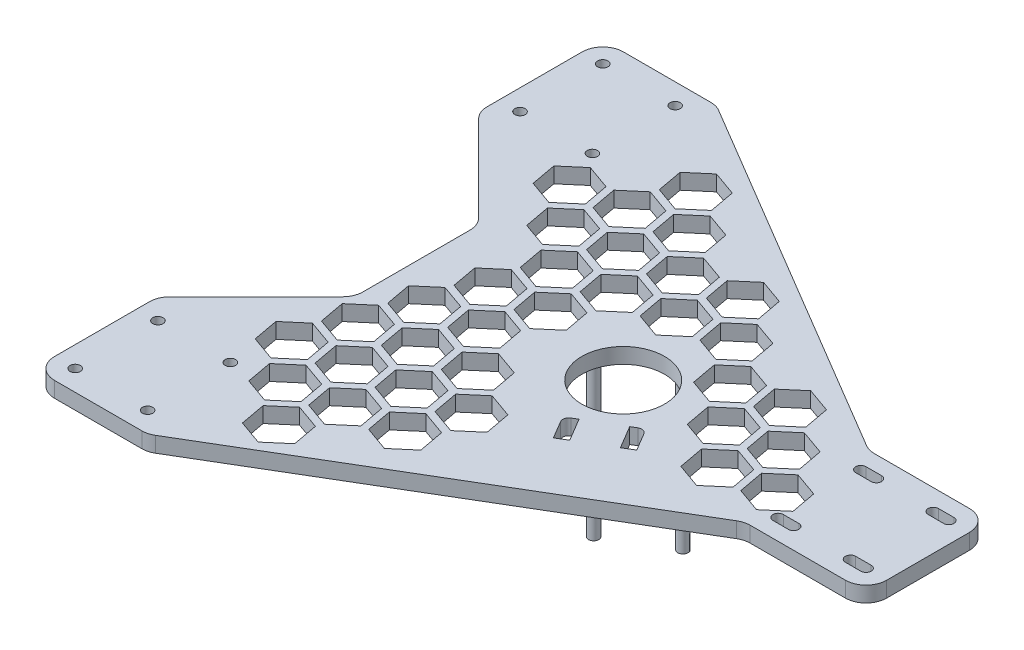
SolidWorks part; units mm, degrees
material "6061-O (SS)"
ref_plane "Plan de face" through (0, 0, 0) normal (0, 0, 1) x (1, 0, 0)
ref_plane "Plan de dessus" through (0, 0, 0) normal (0, 1, 0) x (1, 0, 0)
ref_plane "Plan de droite" through (0, 0, 0) normal (1, 0, 0) x (0, 0, -1)
sketch "Esquisse1" plane through (0, 0, 0) normal (0, 1, 0) x (1, 0, 0)
  line L1 (58.95, -55) -> (-58.95, -55)
  line L2 (58.95, -55) -> (58.95, 55)
  line L3 (58.95, 55) -> (-58.95, 55)
  line L4 (-58.95, -55) -> (-58.95, 55)
  line L5 (58.95, -55) -> (-58.95, 55) construction
  line L6 (58.95, 55) -> (-58.95, -55) construction
  point P0 (0, 0)
  dimension "D1" = 110
  dimension "D2" = 117.9
extrude "Boss.-Extru.1" add sketch "Esquisse1" along normal blind 3
sketch "Esquisse2" plane through (0, 0, 0) normal (0, 1, 0) x (1, 0, 0)
  line L0 (-58.95, -55) -> (58.95, -55) construction
  line L1 (-54.95, -35) -> (-40.95, -35) construction
  line L2 (-54.95, -35) -> (-54.95, -51) construction
  line L3 (-54.95, -51) -> (-40.95, -51) construction
  line L4 (-40.95, -35) -> (-40.95, -51) construction
  line L5 (-54.95, -35) -> (-40.95, -51) construction
  line L6 (-54.95, -51) -> (-40.95, -35) construction
  line L7 (-58.95, 55) -> (-58.95, -55) construction
  line L8 (0, 0) -> (-58.95, 0) construction
  line L9 (-54.95, 51) -> (-40.95, 35) construction
  line L10 (-54.95, 35) -> (-40.95, 51) construction
  line L11 (-40.95, 35) -> (-40.95, 51) construction
  line L12 (-54.95, 51) -> (-40.95, 51) construction
  line L13 (-54.95, 35) -> (-54.95, 51) construction
  line L14 (-54.95, 35) -> (-40.95, 35) construction
  line L15 (46.45, 0) -> (53.45, 8) construction
  line L16 (39.45, 8) -> (53.45, 8) construction
  line L17 (39.45, 8) -> (39.45, -8) construction
  line L18 (39.45, -8) -> (53.45, -8) construction
  line L19 (53.45, 8) -> (53.45, -8) construction
  line L20 (39.45, 8) -> (46.45, 0) construction
  line L21 (39.45, -8) -> (46.45, 0) construction
  line L22 (46.45, 0) -> (53.45, -8) construction
  line L23 (0, 0) -> (58.95, 0) construction
  line L24 (58.95, -55) -> (58.95, 55) construction
  line L25 (58.95, 12) -> (35.45, 12)
  line L26 (35.45, 12) -> (-36.95, 55)
  line L27 (58.95, 55) -> (-58.95, 55) construction
  line L28 (-36.95, 55) -> (58.95, 55)
  line L29 (58.95, 55) -> (58.95, 12)
  line L30 (58.95, -12) -> (35.45, -12)
  line L31 (58.95, -55) -> (58.95, -12)
  line L32 (-36.95, -55) -> (58.95, -55)
  line L33 (35.45, -12) -> (-36.95, -55)
  line L34 (-58.95, -31) -> (-39.95, -12)
  line L35 (-39.95, -12) -> (-39.95, 12)
  line L36 (-39.95, 12) -> (-58.95, 31)
  line L37 (-58.95, 31) -> (-58.95, -31)
  line L38 (37.95, 8) -> (40.95, 8) construction
  line L39 (37.95, 9) -> (40.95, 9)
  line L40 (37.95, 7) -> (40.95, 7)
  line L41 (54.95, 8) -> (51.95, 8) construction
  line L42 (54.95, 7) -> (51.95, 7)
  line L43 (54.95, 9) -> (51.95, 9)
  line L44 (37.95, -8) -> (40.95, -8) construction
  line L45 (37.95, -7) -> (40.95, -7)
  line L46 (37.95, -9) -> (40.95, -9)
  line L47 (54.95, -8) -> (51.95, -8) construction
  line L48 (54.95, -9) -> (51.95, -9)
  line L49 (54.95, -7) -> (51.95, -7)
  circle A0 centre (-40.95, -35) radius 1
  circle A1 centre (-54.95, -35) radius 1
  circle A2 centre (-54.95, -51) radius 1
  circle A3 centre (-40.95, -51) radius 1
  circle A4 centre (-40.95, 51) radius 1
  circle A5 centre (-54.95, 51) radius 1
  circle A6 centre (-54.95, 35) radius 1
  circle A7 centre (-40.95, 35) radius 1
  arc A12 (37.95, 9) -> (37.95, 7) centre (37.95, 8) ccw
  arc A13 (40.95, 7) -> (40.95, 9) centre (40.95, 8) ccw
  arc A14 (54.95, 7) -> (54.95, 9) centre (54.95, 8) ccw
  arc A15 (51.95, 9) -> (51.95, 7) centre (51.95, 8) ccw
  arc A16 (37.95, -7) -> (37.95, -9) centre (37.95, -8) ccw
  arc A17 (40.95, -9) -> (40.95, -7) centre (40.95, -8) ccw
  arc A18 (54.95, -9) -> (54.95, -7) centre (54.95, -8) ccw
  arc A19 (51.95, -7) -> (51.95, -9) centre (51.95, -8) ccw
  point P0 (-47.95, -43)
  point P25 (-47.95, 43)
  point P26 (46.45, 0)
  point P33 (39.45, 8)
  point P52 (-39.95, 0)
  point P58 (53.45, 8)
  point P65 (39.45, -8)
  point P72 (53.45, -8)
  dimension "D3" = 2
  dimension "D4" = 4
  dimension "D5" = 4
  dimension "D6" = 1
  dimension "D1" = 16
  dimension "D2" = 14
  dimension "D7" = 14
  dimension "D8" = 16
  dimension "D9" = 5.5
  dimension "D10" = 4
  dimension "D11" = 4
  dimension "D12" = 4
  dimension "D13" = 4
  dimension "D14" = 4
  dimension "D15" = 4
  dimension "D16" = 1
  dimension "D17" = 1.5
extrude "Enlèv. mat.-Extru.1" cut sketch "Esquisse2" along normal through all
fillet "Congé1" radius 4 12 edges at (35.45, 1.5, 12) (58.95, 1.5, 12) (58.95, 1.5, -12) (35.45, 1.5, -12) (-36.95, 1.5, -55) (-58.95, 1.5, -55) (-58.95, 1.5, -31) (-39.95, 1.5, -12) (-39.95, 1.5, 12) (-58.95, 1.5, 31) (-58.95, 1.5, 55) (-36.95, 1.5, 55)
sketch "Esquisse3" plane through (0, 0, 0) normal (0, 1, 0) x (1, 0, 0)
  line L1 (11, -11) -> (-11, -11) construction
  line L2 (11, -11) -> (11, 11) construction
  line L3 (11, 11) -> (-11, 11) construction
  line L4 (-11, -11) -> (-11, 11) construction
  line L5 (11, -11) -> (-11, 11) construction
  line L6 (11, 11) -> (-11, -11) construction
  line L7 (-11.5, 11) -> (-10.5, 11) construction
  line L8 (-11.5, 13) -> (-10.5, 13)
  line L9 (-11.5, 9) -> (-10.5, 9)
  line L10 (0, 0) -> (-11, 0) construction
  line L11 (0, 0) -> (0, 11) construction
  line L12 (11.5, 11) -> (10.5, 11) construction
  line L13 (11.5, 13) -> (10.5, 13)
  line L14 (11.5, 9) -> (10.5, 9)
  line L15 (11.5, -11) -> (10.5, -11) construction
  line L16 (11.5, -13) -> (10.5, -13)
  line L17 (11.5, -9) -> (10.5, -9)
  line L18 (-11.5, -11) -> (-10.5, -11) construction
  line L19 (-11.5, -13) -> (-10.5, -13)
  line L20 (-11.5, -9) -> (-10.5, -9)
  arc A4 (-11.5, 13) -> (-11.5, 9) centre (-11.5, 11) ccw
  arc A5 (-10.5, 9) -> (-10.5, 13) centre (-10.5, 11) ccw
  arc A6 (11.5, 13) -> (11.5, 9) centre (11.5, 11) cw
  arc A7 (10.5, 9) -> (10.5, 13) centre (10.5, 11) cw
  arc A8 (11.5, -13) -> (11.5, -9) centre (11.5, -11) ccw
  arc A9 (10.5, -9) -> (10.5, -13) centre (10.5, -11) ccw
  arc A10 (-11.5, -13) -> (-11.5, -9) centre (-11.5, -11) cw
  arc A11 (-10.5, -9) -> (-10.5, -13) centre (-10.5, -11) cw
  circle A12 centre (0, 0) radius 8
  point P0 (0, 0)
  point P8 (-11, 11)
  point P22 (11, 11)
  point P29 (11, -11)
  point P36 (-11, -11)
  dimension "D3" = 2
  dimension "D6" = 16
  dimension "D1" = 22
  dimension "D2" = 22
  dimension "D5" = 0.5
extrude "Enlèv. mat.-Extru.2" cut sketch "Esquisse3" along normal through all contours A12
sketch "Esquisse4" plane through (0, 0, 0) normal (0, -1, 0) x (1, 0, 0)
  line L4 (0, 0) -> (6.2905, 0) construction
  line L11 (2.9021, 16.3913) -> (0.8595, 12.9521)
  line L13 (1.261, 11.3761) -> (2.2498, 10.7889)
  line L18 (2.2498, 10.7889) -> (4.8796, 15.2168)
  line L19 (4.8796, 15.2168) -> (2.9021, 16.3913)
  line L21 (3.5647, 13.0028) -> (9.7122, 9.3517) construction
  line L22 (7.939, 13.3671) -> (7.3805, 12.4266) construction
  line L23 (0.2722, 11.9634) -> (2.2498, 10.7889) construction
  line L24 (34.5057, 12.5608) -> (-36.0057, 54.4392) construction
  line L25 (0.2722, 11.9634) -> (0.8595, 12.9521) construction
  line L26 (8.3973, 7.1377) -> (11.0271, 11.5657)
  line L27 (9.386, 6.5505) -> (8.3973, 7.1377)
  line L28 (13.0046, 10.3912) -> (10.962, 6.952)
  line L29 (11.0271, 11.5657) -> (13.0046, 10.3912)
  line L36 (-36.0057, -54.4392) -> (34.5057, -12.5608) construction
  line L37 (-20.806, -41.8884) -> (-19.896, -36.9719)
  line L38 (-19.896, -36.9719) -> (-23.6988, -33.7255)
  line L39 (-23.6988, -33.7255) -> (-28.4116, -35.3956)
  line L40 (-28.4116, -35.3956) -> (-29.3216, -40.3121)
  line L41 (-29.3216, -40.3121) -> (-25.5189, -43.5585)
  line L42 (-25.5189, -43.5585) -> (-20.806, -41.8884)
  line L91 (-39.95, 0) -> (-65.3468, 0) construction
  line L92 (-24.2263, -32.4915) -> (-23.3162, -27.575)
  line L153 (-23.3162, -27.575) -> (-27.119, -24.3286)
  line L154 (-27.119, -24.3286) -> (-31.8318, -25.9987)
  line L155 (-31.8318, -25.9987) -> (-32.7418, -30.9152)
  line L156 (-32.7418, -30.9152) -> (-28.9391, -34.1616)
  line L157 (-28.9391, -34.1616) -> (-24.2263, -32.4915)
  line L158 (-27.6465, -23.0945) -> (-26.7364, -18.178)
  line L159 (-26.7364, -18.178) -> (-30.5392, -14.9317)
  line L160 (-30.5392, -14.9317) -> (-35.252, -16.6018)
  line L161 (-35.252, -16.6018) -> (-36.162, -21.5183)
  line L162 (-36.162, -21.5183) -> (-32.3593, -24.7646)
  line L163 (-32.3593, -24.7646) -> (-27.6465, -23.0945)
  line L164 (-14.3782, -34.2279) -> (-13.4681, -29.3115)
  line L165 (-13.4681, -29.3115) -> (-17.2709, -26.0651)
  line L166 (-17.2709, -26.0651) -> (-21.9837, -27.7352)
  line L167 (-21.9837, -27.7352) -> (-22.8938, -32.6517)
  line L168 (-22.8938, -32.6517) -> (-19.091, -35.898)
  line L169 (-19.091, -35.898) -> (-14.3782, -34.2279)
  line L170 (-17.8041, -24.8152) -> (-16.8941, -19.8987)
  line L171 (-16.8941, -19.8987) -> (-20.6968, -16.6524)
  line L172 (-20.6968, -16.6524) -> (-25.4097, -18.3225)
  line L173 (-25.4097, -18.3225) -> (-26.3197, -23.239)
  line L174 (-26.3197, -23.239) -> (-22.5169, -26.4853)
  line L175 (-22.5169, -26.4853) -> (-17.8041, -24.8152)
  line L176 (-34.0743, -30.755) -> (-33.1643, -25.8385)
  line L177 (-33.1643, -25.8385) -> (-36.967, -22.5921)
  line L178 (-36.967, -22.5921) -> (-41.6799, -24.2622)
  line L179 (-41.6799, -24.2622) -> (-42.5899, -29.1787)
  line L180 (-42.5899, -29.1787) -> (-38.7872, -32.4251)
  line L181 (-38.7872, -32.4251) -> (-34.0743, -30.755)
  line L182 (-11.3762, -17.1548) -> (-10.4662, -12.2383)
  line L183 (-10.4662, -12.2383) -> (-14.269, -8.9919)
  line L184 (-14.269, -8.9919) -> (-18.9818, -10.662)
  line L185 (-18.9818, -10.662) -> (-19.8918, -15.5785)
  line L186 (-19.8918, -15.5785) -> (-16.0891, -18.8249)
  line L187 (-16.0891, -18.8249) -> (-11.3762, -17.1548)
  line L188 (-21.2243, -15.4183) -> (-20.3143, -10.5018)
  line L189 (-20.3143, -10.5018) -> (-24.117, -7.2554)
  line L190 (-24.117, -7.2554) -> (-28.8299, -8.9256)
  line L191 (-28.8299, -8.9256) -> (-29.7399, -13.842)
  line L192 (-29.7399, -13.842) -> (-25.9371, -17.0884)
  line L193 (-25.9371, -17.0884) -> (-21.2243, -15.4183)
  line L194 (-24.6388, -6.0372) -> (-23.7287, -1.1207)
  line L195 (-23.7287, -1.1207) -> (-27.5315, 2.1257)
  line L196 (-27.5315, 2.1257) -> (-32.2443, 0.4556)
  line L197 (-32.2443, 0.4556) -> (-33.1544, -4.4609)
  line L198 (-33.1544, -4.4609) -> (-29.3516, -7.7073)
  line L199 (-29.3516, -7.7073) -> (-24.6388, -6.0372)
  line L200 (-14.7907, -7.7736) -> (-13.8806, -2.8572)
  line L201 (-13.8806, -2.8572) -> (-17.6834, 0.3892)
  line L202 (-17.6834, 0.3892) -> (-22.3962, -1.2809)
  line L203 (-22.3962, -1.2809) -> (-23.3063, -6.1974)
  line L204 (-23.3063, -6.1974) -> (-19.5035, -9.4438)
  line L205 (-19.5035, -9.4438) -> (-14.7907, -7.7736)
  line L206 (-18.2109, 1.6233) -> (-17.3008, 6.5398)
  line L207 (-17.3008, 6.5398) -> (-21.1036, 9.7861)
  line L208 (-21.1036, 9.7861) -> (-25.8164, 8.116)
  line L209 (-25.8164, 8.116) -> (-26.7265, 3.1995)
  line L210 (-26.7265, 3.1995) -> (-22.9237, -0.0468)
  line L211 (-22.9237, -0.0468) -> (-18.2109, 1.6233)
  line L212 (-21.6311, 11.0202) -> (-20.7211, 15.9367)
  line L213 (-20.7211, 15.9367) -> (-24.5238, 19.1831)
  line L214 (-24.5238, 19.1831) -> (-29.2366, 17.513)
  line L215 (-29.2366, 17.513) -> (-30.1467, 12.5965)
  line L216 (-30.1467, 12.5965) -> (-26.3439, 9.3501)
  line L217 (-26.3439, 9.3501) -> (-21.6311, 11.0202)
  line L218 (-25.0513, 20.4171) -> (-24.1413, 25.3336)
  line L219 (-24.1413, 25.3336) -> (-27.944, 28.58)
  line L220 (-27.944, 28.58) -> (-32.6568, 26.9099)
  line L221 (-32.6568, 26.9099) -> (-33.5669, 21.9934)
  line L222 (-33.5669, 21.9934) -> (-29.7641, 18.747)
  line L223 (-29.7641, 18.747) -> (-25.0513, 20.4171)
  line L224 (-28.4715, 29.8141) -> (-27.5615, 34.7305)
  line L225 (-27.5615, 34.7305) -> (-31.3642, 37.9769)
  line L226 (-31.3642, 37.9769) -> (-36.0771, 36.3068)
  line L227 (-36.0771, 36.3068) -> (-36.9871, 31.3903)
  line L228 (-36.9871, 31.3903) -> (-33.1843, 28.144)
  line L229 (-33.1843, 28.144) -> (-28.4715, 29.8141)
  line L230 (-28.059, 3.3598) -> (-27.1489, 8.2763)
  line L231 (-27.1489, 8.2763) -> (-30.9517, 11.5226)
  line L232 (-30.9517, 11.5226) -> (-35.6645, 9.8525)
  line L233 (-35.6645, 9.8525) -> (-36.5746, 4.936)
  line L234 (-36.5746, 4.936) -> (-32.7718, 1.6897)
  line L235 (-32.7718, 1.6897) -> (-28.059, 3.3598)
  line L236 (-15.2032, 18.6807) -> (-14.2932, 23.5971)
  line L237 (-14.2932, 23.5971) -> (-18.0959, 26.8435)
  line L238 (-18.0959, 26.8435) -> (-22.8088, 25.1734)
  line L239 (-22.8088, 25.1734) -> (-23.7188, 20.2569)
  line L240 (-23.7188, 20.2569) -> (-19.9161, 17.0105)
  line L241 (-19.9161, 17.0105) -> (-15.2032, 18.6807)
  line L242 (-8.7754, 26.3411) -> (-7.8653, 31.2576)
  line L243 (-7.8653, 31.2576) -> (-11.6681, 34.504)
  line L244 (-11.6681, 34.504) -> (-16.3809, 32.8338)
  line L245 (-16.3809, 32.8338) -> (-17.2909, 27.9174)
  line L246 (-17.2909, 27.9174) -> (-13.4882, 24.671)
  line L247 (-13.4882, 24.671) -> (-8.7754, 26.3411)
  line L248 (-18.6234, 28.0776) -> (-17.7134, 32.9941)
  line L249 (-17.7134, 32.9941) -> (-21.5161, 36.2404)
  line L250 (-21.5161, 36.2404) -> (-26.229, 34.5703)
  line L251 (-26.229, 34.5703) -> (-27.139, 29.6538)
  line L252 (-27.139, 29.6538) -> (-23.3363, 26.4075)
  line L253 (-23.3363, 26.4075) -> (-18.6234, 28.0776)
  line L254 (-22.0436, 37.4745) -> (-21.1336, 42.391)
  line L255 (-21.1336, 42.391) -> (-24.9363, 45.6374)
  line L256 (-24.9363, 45.6374) -> (-29.6492, 43.9672)
  line L257 (-29.6492, 43.9672) -> (-30.5592, 39.0508)
  line L258 (-30.5592, 39.0508) -> (-26.7565, 35.8044)
  line L259 (-26.7565, 35.8044) -> (-22.0436, 37.4745)
  line L260 (-34.8994, 22.1536) -> (-33.9893, 27.0701)
  line L261 (-33.9893, 27.0701) -> (-37.7921, 30.3165)
  line L262 (-37.7921, 30.3165) -> (-42.5049, 28.6464)
  line L263 (-42.5049, 28.6464) -> (-43.415, 23.7299)
  line L264 (-43.415, 23.7299) -> (-39.6122, 20.4835)
  line L265 (-39.6122, 20.4835) -> (-34.8994, 22.1536)
  line L266 (-31.4792, 12.7567) -> (-30.5691, 17.6732)
  line L267 (-30.5691, 17.6732) -> (-34.3719, 20.9195)
  line L268 (-34.3719, 20.9195) -> (-39.0847, 19.2494)
  line L269 (-39.0847, 19.2494) -> (-39.9948, 14.333)
  line L270 (-39.9948, 14.333) -> (-36.192, 11.0866)
  line L271 (-36.192, 11.0866) -> (-31.4792, 12.7567)
  line L272 (-11.783, 9.2837) -> (-10.873, 14.2002)
  line L273 (-10.873, 14.2002) -> (-14.6757, 17.4466)
  line L274 (-14.6757, 17.4466) -> (-19.3886, 15.7765)
  line L275 (-19.3886, 15.7765) -> (-20.2986, 10.86)
  line L276 (-20.2986, 10.86) -> (-16.4959, 7.6136)
  line L277 (-16.4959, 7.6136) -> (-11.783, 9.2837)
  line L278 (-7.956, -26.5517) -> (-7.046, -21.6352)
  line L279 (-7.046, -21.6352) -> (-10.8488, -18.3889)
  line L280 (-10.8488, -18.3889) -> (-15.5616, -20.059)
  line L281 (-15.5616, -20.059) -> (-16.4716, -24.9755)
  line L282 (-16.4716, -24.9755) -> (-12.6689, -28.2218)
  line L283 (-12.6689, -28.2218) -> (-7.956, -26.5517)
  line L284 (-1.5282, -18.8913) -> (-0.6181, -13.9748)
  line L285 (-0.6181, -13.9748) -> (-4.4209, -10.7284)
  line L286 (-4.4209, -10.7284) -> (-9.1337, -12.3985)
  line L287 (-9.1337, -12.3985) -> (-10.0438, -17.315)
  line L288 (-10.0438, -17.315) -> (-6.241, -20.5614)
  line L289 (-6.241, -20.5614) -> (-1.5282, -18.8913)
  line L290 (8.3199, -20.6277) -> (9.23, -15.7113)
  line L291 (9.23, -15.7113) -> (5.4272, -12.4649)
  line L292 (5.4272, -12.4649) -> (0.7144, -14.135)
  line L293 (0.7144, -14.135) -> (-0.1957, -19.0515)
  line L294 (-0.1957, -19.0515) -> (3.6071, -22.2979)
  line L295 (3.6071, -22.2979) -> (8.3199, -20.6277)
  line L296 (14.7478, -12.9673) -> (15.6578, -8.0508)
  line L297 (15.6578, -8.0508) -> (11.8551, -4.8044)
  line L298 (11.8551, -4.8044) -> (7.1422, -6.4746)
  line L299 (7.1422, -6.4746) -> (6.2322, -11.391)
  line L300 (6.2322, -11.391) -> (10.035, -14.6374)
  line L301 (10.035, -14.6374) -> (14.7478, -12.9673)
  line L302 (21.1757, -5.3069) -> (22.0857, -0.3904)
  line L303 (22.0857, -0.3904) -> (18.2829, 2.856)
  line L304 (18.2829, 2.856) -> (13.5701, 1.1859)
  line L305 (13.5701, 1.1859) -> (12.6601, -3.7306)
  line L306 (12.6601, -3.7306) -> (16.4628, -6.977)
  line L307 (16.4628, -6.977) -> (21.1757, -5.3069)
  line L308 (27.6035, 2.3536) -> (28.5136, 7.2701)
  line L309 (28.5136, 7.2701) -> (24.7108, 10.5164)
  line L310 (24.7108, 10.5164) -> (19.998, 8.8463)
  line L311 (19.998, 8.8463) -> (19.0879, 3.9298)
  line L312 (19.0879, 3.9298) -> (22.8907, 0.6835)
  line L313 (22.8907, 0.6835) -> (27.6035, 2.3536)
  line L314 (24.5959, -14.7038) -> (25.5059, -9.7873)
  line L315 (25.5059, -9.7873) -> (21.7031, -6.5409)
  line L316 (21.7031, -6.5409) -> (16.9903, -8.211)
  line L317 (16.9903, -8.211) -> (16.0803, -13.1275)
  line L318 (16.0803, -13.1275) -> (19.883, -16.3739)
  line L319 (19.883, -16.3739) -> (24.5959, -14.7038)
  line L320 (31.0237, -7.0433) -> (31.9338, -2.1269)
  line L321 (31.9338, -2.1269) -> (28.131, 1.1195)
  line L322 (28.131, 1.1195) -> (23.4182, -0.5506)
  line L323 (23.4182, -0.5506) -> (22.5081, -5.4671)
  line L324 (22.5081, -5.4671) -> (26.3109, -8.7135)
  line L325 (26.3109, -8.7135) -> (31.0237, -7.0433)
  line L326 (37.4516, 0.6171) -> (38.3617, 5.5336)
  line L327 (38.3617, 5.5336) -> (34.5589, 8.78)
  line L328 (34.5589, 8.78) -> (29.8461, 7.1098)
  line L329 (29.8461, 7.1098) -> (28.936, 2.1934)
  line L330 (28.936, 2.1934) -> (32.7388, -1.053)
  line L331 (32.7388, -1.053) -> (37.4516, 0.6171)
  line L332 (-5.3551, 16.9442) -> (-4.4451, 21.8607)
  line L333 (-4.4451, 21.8607) -> (-8.2479, 25.107)
  line L334 (-8.2479, 25.107) -> (-12.9607, 23.4369)
  line L335 (-12.9607, 23.4369) -> (-13.8707, 18.5204)
  line L336 (-13.8707, 18.5204) -> (-10.068, 15.2741)
  line L337 (-10.068, 15.2741) -> (-5.3551, 16.9442)
  line L338 (1.892, -28.2882) -> (2.8021, -23.3717)
  line L339 (2.8021, -23.3717) -> (-1.0007, -20.1253)
  line L340 (-1.0007, -20.1253) -> (-5.7135, -21.7954)
  line L341 (-5.7135, -21.7954) -> (-6.6236, -26.7119)
  line L342 (-6.6236, -26.7119) -> (-2.8208, -29.9583)
  line L343 (-2.8208, -29.9583) -> (1.892, -28.2882)
  arc A14 (1.261, 11.3761) -> (0.8595, 12.9521) centre (1.8483, 12.3649) cw
  arc A15 (9.386, 6.5505) -> (10.962, 6.952) centre (9.9733, 7.5393) ccw
  circle A16 centre (-24.6088, -38.642) radius 4.3301 construction
  point P8 (6.6384, 11.1773)
  point P37 (0.2722, 11.9634)
  dimension "D1" = 7.15
  dimension "D2" = 5.15
  dimension "D3" = 2.3
  dimension "D5" = 1.15
  dimension "D12" = 2
  dimension "D13" = 2
  dimension "D4" = 13
  dimension "D6" = 5
  dimension "D7" = 3
  dimension "D8" = 2
  dimension "D9" = 2
  dimension "D10" = 2
  dimension "D11" = 2
  dimension "D21" = 4
  dimension "D25" = 11.194
  dimension "D26" = 3
  dimension "D14" = 2
  dimension "D16" = 2
  dimension "D15" = 2
  dimension "D18" = 5
  dimension "D17" = 2
  dimension "D19" = 3
  dimension "D20" = 2
  dimension "D22" = 2
  dimension "D23" = 3
  dimension "D24" = 2
extrude "Enlèv. mat.-Extru.3" cut sketch "Esquisse4" against normal through all
sketch "Esquisse5" plane through (0, 0, 0) normal (0, -1, 0) x (1, 0, 0)
  line L0 (102137.6395, 171971.2813) -> (-102122.32, -171945.4876) construction
  line L2 (-6.5068, -10.9556) -> (-7.4595, -12.5598) construction
  circle A0 centre (-9.6727, -3.9488) radius 1
  circle A1 centre (1.1607, -10.383) radius 1
  dimension "D1" = 2
  dimension "D2" = 6.3
  dimension "D3" = 10.4476
extrude "Boss.-Extru.2" add sketch "Esquisse5" along normal blind 30
